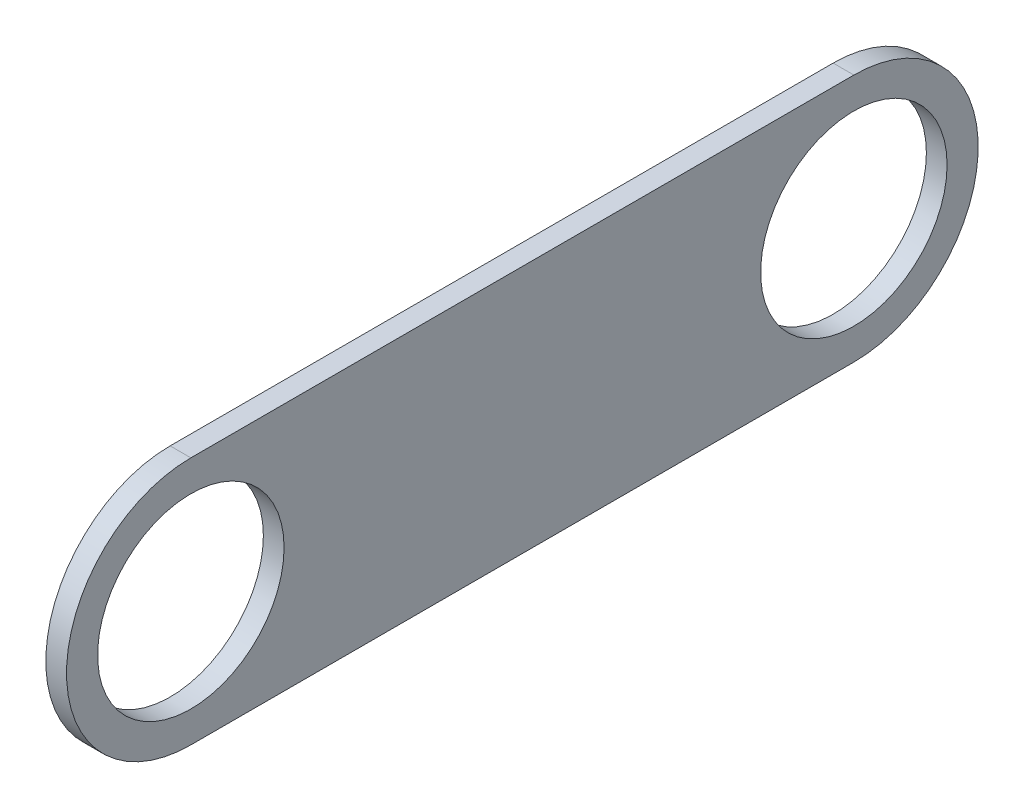
SolidWorks part; units mm, degrees
ref_plane "Front" through (0, 0, 0) normal (0, 0, 1) x (1, 0, 0)
ref_plane "Top" through (0, 0, 0) normal (0, 1, 0) x (1, 0, 0)
ref_plane "Right" through (0, 0, 0) normal (1, 0, 0) x (0, 0, -1)
sketch "Sketch1" plane through (0, 0, 0) normal (1, 0, 0) x (0, 0, -1)
  line L0 (-50.8, 0) -> (50.8, 0) construction
  line L1 (-50.8, 19.05) -> (50.8, 19.05)
  line L2 (-50.8, -19.05) -> (50.8, -19.05)
  arc A0 (-50.8, 19.05) -> (-50.8, -19.05) centre (-50.8, 0) ccw
  arc A1 (50.8, -19.05) -> (50.8, 19.05) centre (50.8, 0) ccw
  circle A2 centre (50.8, 0) radius 14.2875
  circle A3 centre (-50.8, 0) radius 14.2875
  point P2 (0, 0)
  dimension "D1" = 4.7625
  dimension "D2" = 28.575
  dimension "D3" = 101.6
extrude "Boss-Extrude1" add sketch "Sketch1" along normal blind 3.175
